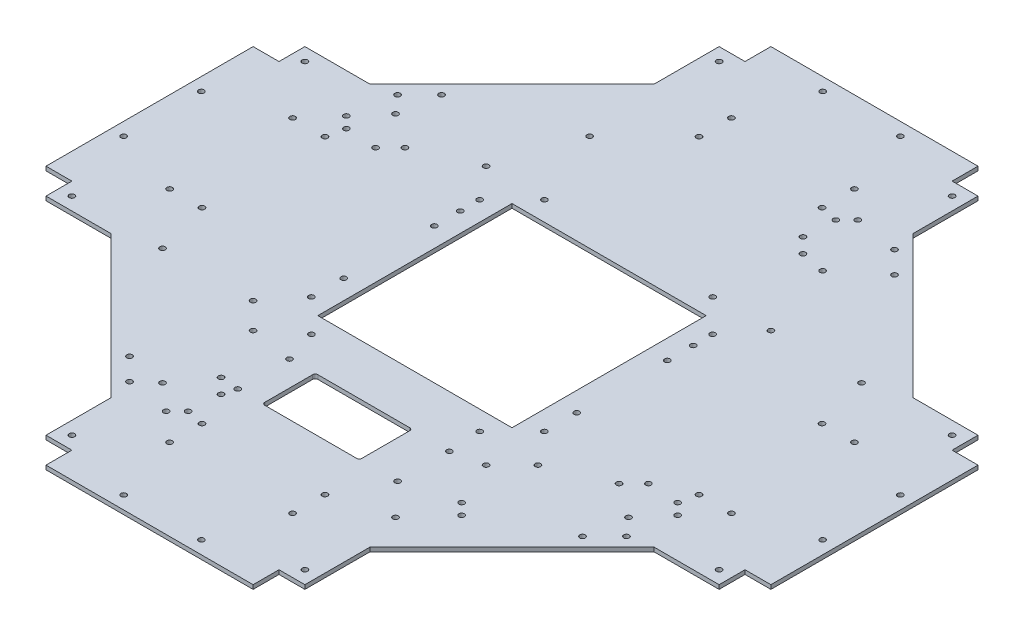
SolidWorks part; units mm, degrees
ref_plane "Front Plane" through (0, 0, 0) normal (0, 0, 1) x (1, 0, 0)
ref_plane "Top Plane" through (0, 0, 0) normal (0, 1, 0) x (1, 0, 0)
ref_plane "Right Plane" through (0, 0, 0) normal (1, 0, 0) x (0, 0, -1)
sketch "Sketch1" plane through (0, 0, 0) normal (0, 1, 0) x (1, 0, 0)
  line L0 (0, -280) -> (100, -280)
  line L1 (100, -280) -> (100, -209.6016)
  line L2 (280, -100) -> (209.6016, -100)
  line L3 (0, 0) -> (0, -280) construction
  line L4 (280, 0) -> (280, -100)
  line L5 (-280, 280) -> (280, 280) construction
  line L6 (-280, 280) -> (-280, -280) construction
  line L7 (-280, -280) -> (280, -280) construction
  line L8 (280, 280) -> (280, -280) construction
  line L9 (-280, 280) -> (280, -280) construction
  line L10 (-280, -280) -> (280, 280) construction
  line L11 (100, -209.6016) -> (209.6016, -100)
  line L12 (-280, 0) -> (-280, -100)
  line L13 (-280, -100) -> (-209.6016, -100)
  line L14 (-209.6016, -100) -> (-100, -209.6016)
  line L15 (-100, -280) -> (-100, -209.6016)
  line L16 (0, -280) -> (-100, -280)
  line L17 (0, 280) -> (-100, 280)
  line L18 (-100, 280) -> (-100, 209.6016)
  line L19 (-100, 209.6016) -> (-209.6016, 100)
  line L20 (-280, 100) -> (-209.6016, 100)
  line L21 (-280, 0) -> (-280, 100)
  line L22 (280, 0) -> (280, 100)
  line L23 (280, 100) -> (209.6016, 100)
  line L24 (209.6016, 100) -> (100, 209.6016)
  line L25 (100, 280) -> (100, 209.6016)
  line L26 (0, 280) -> (100, 280)
  line L27 (111.5258, -219.2889) -> (219.2889, -111.5258) construction
  line L28 (219.2889, -111.5258) -> (247.5732, -139.8101) construction
  line L29 (247.5732, -139.8101) -> (139.8101, -247.5732) construction
  line L30 (139.8101, -247.5732) -> (111.5258, -219.2889) construction
  line L31 (-100, -270) -> (100, -270) construction
  line L32 (-90, -280) -> (-90, 280) construction
  line L37 (-70, -70) -> (70, 70) construction
  line L38 (-70, 70) -> (70, -70) construction
  line L39 (-100, -260) -> (100, -260) construction
  line L40 (-280, 40) -> (280, 40) construction
  line L41 (0, 280) -> (0, 0) construction
  line L42 (-280, -90) -> (280, -90) construction
  line L43 (-260, -100) -> (-260, 100) construction
  line L44 (0, 0) -> (-280, 0) construction
  arc A0 (100, -280) -> (280, -100) centre (100, -100) ccw construction
  circle A1 centre (-47.5, -192) radius 2.125
  circle A2 centre (-47.5, -217) radius 2.125
  circle A3 centre (47.5, -217) radius 2.125
  circle A4 centre (47.5, -192) radius 2.125
  circle A5 centre (-192, 47.5) radius 2.125
  circle A6 centre (-217, 47.5) radius 2.125
  circle A7 centre (-192, -47.5) radius 2.125
  circle A8 centre (-217, -47.5) radius 2.125
  circle A9 centre (47.5, 192) radius 2.125
  circle A10 centre (47.5, 217) radius 2.125
  circle A11 centre (-47.5, 192) radius 2.125
  circle A12 centre (-47.5, 217) radius 2.125
  circle A13 centre (192, -47.5) radius 2.125
  circle A14 centre (217, -47.5) radius 2.125
  circle A15 centre (192, 47.5) radius 2.125
  circle A16 centre (217, 47.5) radius 2.125
  circle A17 centre (-90, -270) radius 2.125
  circle A18 centre (-30, -270) radius 2.125
  circle A19 centre (30, -270) radius 2.125
  circle A20 centre (90, -270) radius 2.125
  circle A21 centre (-270, 90) radius 2.125
  circle A22 centre (-270, 30) radius 2.125
  circle A23 centre (-270, -30) radius 2.125
  circle A24 centre (-270, -90) radius 2.125
  circle A25 centre (90, 270) radius 2.125
  circle A26 centre (30, 270) radius 2.125
  circle A27 centre (-30, 270) radius 2.125
  circle A28 centre (-90, 270) radius 2.125
  circle A29 centre (270, -90) radius 2.125
  circle A30 centre (270, -30) radius 2.125
  circle A31 centre (270, 30) radius 2.125
  circle A32 centre (270, 90) radius 2.125
  circle A33 centre (-90, -250) radius 2.125
  circle A34 centre (-90, -180) radius 2.125
  circle A35 centre (-90, -110) radius 2.125
  circle A36 centre (-90, -40) radius 2.125
  circle A37 centre (-90, 30) radius 2.125
  circle A38 centre (-90, 50) radius 2.125
  circle A39 centre (-90, 100) radius 2.125 construction
  circle A40 centre (-90, 150) radius 2.125
  circle A41 centre (-90, 200) radius 2.125 construction
  circle A42 centre (-90, 250) radius 2.125
  circle A43 centre (90, -250) radius 2.125
  circle A44 centre (90, -180) radius 2.125
  circle A45 centre (90, -110) radius 2.125
  circle A46 centre (90, -40) radius 2.125
  circle A47 centre (90, 30) radius 2.125
  circle A48 centre (90, 50) radius 2.125
  circle A49 centre (90, 100) radius 2.125 construction
  circle A50 centre (90, 150) radius 2.125
  circle A51 centre (90, 200) radius 2.125 construction
  circle A52 centre (90, 250) radius 2.125
  circle A53 centre (-250, -90) radius 2.125
  circle A54 centre (-180, -90) radius 2.125
  circle A55 centre (-110, -90) radius 2.125
  circle A56 centre (-110, 90) radius 2.125
  circle A57 centre (-180, 90) radius 2.125
  circle A58 centre (-250, 90) radius 2.125
  circle A59 centre (110, -90) radius 2.125
  circle A60 centre (180, -90) radius 2.125
  circle A61 centre (250, -90) radius 2.125
  circle A62 centre (110, 90) radius 2.125
  circle A63 centre (180, 90) radius 2.125
  circle A64 centre (250, 90) radius 2.125
  point P33 (0, 0)
  point P68 (0, 0)
  point P107 (0, 0)
  dimension "D10" = 25
  dimension "4.25" = 4.25
  dimension "D11" = 4.25
  dimension "D16" = 4.25
  dimension "D24" = 4.25
  dimension "D28" = 4.25
  dimension "D32" = 4.25
  dimension "D1" = 560
  dimension "D2" = 90
  dimension "D3" = 280
  dimension "D4" = 4
  dimension "D5" = 100
  dimension "D6" = 155
  dimension "D7" = 152.4
  dimension "D8" = 15
  dimension "D9" = 40
  dimension "D12" = 47.5
  dimension "D13" = 63
  dimension "D15" = 10
  dimension "D17" = 10
  dimension "D18" = 76.2
  dimension "D23" = 10
  dimension "D25" = 10
  dimension "D26" = 300
  dimension "D29" = 10
  dimension "D31" = 20
  dimension "D33" = 10
  dimension "D21" = 4
  dimension "D27" = 5
  dimension "D30" = 5
  dimension "D34" = 3
  dimension "D14" = 4
  dimension "D22" = 4
extrude "Boss-Extrude1" add sketch "Sketch1" along normal blind 3.175 contours L26 L17 L18 L19 L20 L21 L12 L13 L14 L15 L16 L0 L1 L11 L2 L4 L22 L23 L24 L25 region at (0, 0, -0.0137)
sketch "Sketch2" plane through (0, 3.175, 0) normal (0, 1, 0) x (1, 0, 0)
  line L0 (-90, -280) -> (-90, 280) construction
  line L1 (-75, -75) -> (75, -75)
  line L2 (-75, -75) -> (-75, 75)
  line L3 (-75, 75) -> (75, 75)
  line L4 (75, -75) -> (75, 75)
  line L5 (-75, -75) -> (75, 75) construction
  line L6 (-75, 75) -> (75, -75) construction
  line L7 (-90, -280) -> (-90, 280) construction
  line L8 (-75, 0) -> (75, 0) construction
  line L9 (0, 75) -> (0, -75) construction
  line L10 (-110, 90) -> (110, 90) construction
  line L11 (37.5, -135) -> (-37.5, -135) construction
  line L16 (-37.5, -155.5) -> (37.5, -155.5)
  line L17 (-37.5, -155.5) -> (-37.5, -114.5)
  line L18 (-37.5, -114.5) -> (37.5, -114.5)
  line L19 (37.5, -155.5) -> (37.5, -114.5)
  line L20 (-37.5, -155.5) -> (37.5, -114.5) construction
  line L21 (-37.5, -114.5) -> (37.5, -155.5) construction
  line L22 (128.2843, -167.1751) -> (98.0356, -136.9265) construction
  line L23 (146.0396, -78.7091) -> (184.862, -39.8867) construction
  line L24 (92.9289, -202.5305) -> (202.5305, -92.9289)
  line L25 (92.9289, -202.5305) -> (202.5305, -92.9289) construction
  line L26 (170.0036, -125.4558) -> (137.8448, -93.2971) construction
  circle A0 centre (66.6, -115) radius 2.125
  circle A1 centre (-90, 65) radius 2.125
  circle A2 centre (-90, -65) radius 2.125
  circle A3 centre (90, -65) radius 2.125
  circle A4 centre (90, 65) radius 2.125
  circle A5 centre (-65, 90) radius 2.125
  circle A6 centre (65, 90) radius 2.125
  circle A7 centre (65, -90) radius 2.125
  circle A8 centre (-65, -90) radius 2.125
  circle A9 centre (66.6, -155) radius 2.125
  circle A10 centre (-56.9, -115) radius 2.1
  circle A11 centre (-56.9, -155) radius 2.1
  circle A12 centre (174.9533, -120.5061) radius 2.125
  circle A13 centre (191.9239, -103.5355) radius 2.125
  circle A14 centre (153.737, -71.0118) radius 2.125
  circle A15 centre (165.0507, -59.6981) radius 2.125
  circle A16 centre (-120.5061, -174.9533) radius 2.125
  circle A17 centre (-103.5355, -191.9239) radius 2.125
  circle A18 centre (-71.0118, -153.737) radius 2.125
  circle A19 centre (-59.6981, -165.0507) radius 2.125
  circle A20 centre (-174.9533, 120.5061) radius 2.125
  circle A21 centre (-191.9239, 103.5355) radius 2.125
  circle A22 centre (-153.737, 71.0118) radius 2.125
  circle A23 centre (-165.0507, 59.6981) radius 2.125
  circle A24 centre (120.5061, 174.9533) radius 2.125
  circle A25 centre (103.5355, 191.9239) radius 2.125
  circle A26 centre (71.0118, 153.737) radius 2.125
  circle A27 centre (59.6981, 165.0507) radius 2.125
  circle A28 centre (114.1421, -153.033) radius 2.125
  circle A29 centre (105.6569, -144.5477) radius 2.1
  circle A30 centre (197.5807, -69.5944) radius 2.125
  circle A31 centre (189.0955, -61.1091) radius 2.1
  circle A32 centre (-61.1091, -189.0955) radius 2.1
  circle A33 centre (-69.5944, -197.5807) radius 2.125
  circle A34 centre (-189.0955, 61.1091) radius 2.1
  circle A35 centre (-197.5807, 69.5944) radius 2.125
  circle A36 centre (61.1091, 189.0955) radius 2.1
  circle A37 centre (69.5944, 197.5807) radius 2.125
  point P0 (0, 0)
  point P6 (0, -135)
  point P86 (0, 0)
  point P111 (0, 0)
  dimension "D3" = 4.25
  dimension "D5" = 4.25
  dimension "D11" = 4.25
  dimension "D14" = 4.2
  dimension "D18" = 4.25
  dimension "D20" = 4.25
  dimension "D23" = 4.25
  dimension "D25" = 4.25
  dimension "D29" = 4.25
  dimension "D31" = 4.2
  dimension "D1" = 150
  dimension "D2" = 150
  dimension "D4" = 10
  dimension "D6" = 10
  dimension "D7" = 75
  dimension "D8" = 41
  dimension "D9" = 0
  dimension "D10" = 135
  dimension "D12" = 20
  dimension "D13" = 66.6
  dimension "D15" = 19.4
  dimension "D16" = 20
  dimension "D19" = 116
  dimension "D21" = 24
  dimension "D22" = 50
  dimension "D24" = 53.85
  dimension "D26" = 16
  dimension "D28" = 50
  dimension "D30" = 20
  dimension "D32" = 12
  dimension "D33" = 59
  dimension "D17" = 10
  dimension "D27" = 4
  dimension "D34" = 4
extrude "Cut-Extrude1" cut sketch "Sketch2" against normal through all
fillet "Fillet1" radius 2 4 edges at (-37.5, 1.5875, 155.5) (37.5, 1.5875, 155.5) (37.5, 1.5875, 114.5) (-37.5, 1.5875, 114.5)
sketch "Sketch3" plane through (0, 3.175, 0) normal (0, 1, 0) x (1, 0, 0)
  line L0 (-260, 80) -> (-280, 80)
  line L1 (80, -260) -> (100, -260)
  line L2 (80, -260) -> (80, -280)
  line L3 (80, -280) -> (100, -280)
  line L4 (100, -260) -> (100, -280)
  line L5 (80, -260) -> (100, -280) construction
  line L6 (80, -280) -> (100, -260) construction
  line L7 (-80, -260) -> (-100, -260)
  line L8 (-80, -260) -> (-80, -280)
  line L9 (-80, -280) -> (-100, -280)
  line L10 (-100, -260) -> (-100, -280)
  line L11 (-80, -260) -> (-100, -280) construction
  line L12 (-80, -280) -> (-100, -260) construction
  line L13 (-260, 80) -> (-260, 100)
  line L14 (-260, 100) -> (-280, 100)
  line L15 (-280, 80) -> (-280, 100)
  line L16 (-260, -80) -> (-280, -80)
  line L17 (-260, -80) -> (-260, -100)
  line L18 (-260, -100) -> (-280, -100)
  line L19 (-280, -80) -> (-280, -100)
  line L20 (80, 260) -> (80, 280)
  line L21 (80, 260) -> (100, 260)
  line L22 (100, 260) -> (100, 280)
  line L23 (80, 280) -> (100, 280)
  line L24 (-80, 260) -> (-80, 280)
  line L25 (-80, 260) -> (-100, 260)
  line L26 (-100, 260) -> (-100, 280)
  line L27 (-80, 280) -> (-100, 280)
  line L28 (260, -80) -> (280, -80)
  line L29 (260, -80) -> (260, -100)
  line L30 (260, -100) -> (280, -100)
  line L31 (280, -80) -> (280, -100)
  line L32 (260, 80) -> (280, 80)
  line L33 (260, 80) -> (260, 100)
  line L34 (260, 100) -> (280, 100)
  line L35 (280, 80) -> (280, 100)
  point P0 (90, -270)
  point P7 (-90, -270)
  point P41 (0, 0)
extrude "Cut-Extrude2" cut sketch "Sketch3" against normal through all
